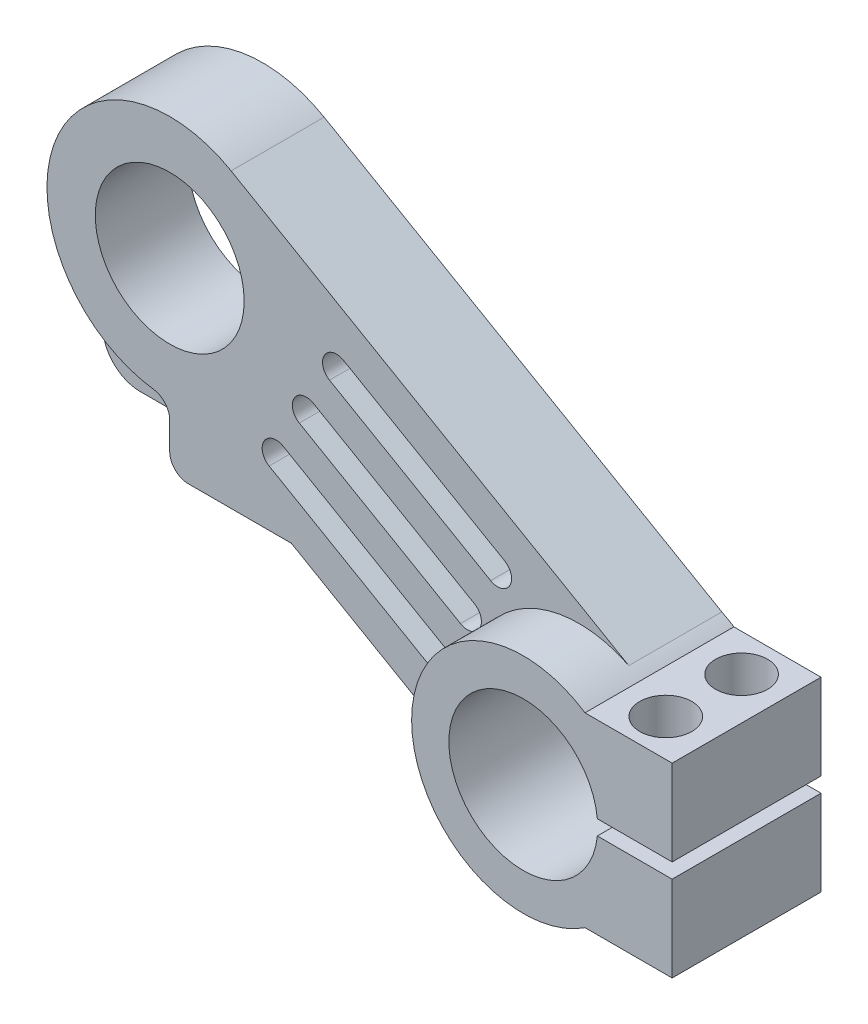
SolidWorks part; units mm, degrees
ref_plane "Alzado" through (0, 0, 0) normal (0, 0, 1) x (1, 0, 0)
ref_plane "Planta" through (0, 0, 0) normal (0, 1, 0) x (1, 0, 0)
ref_plane "Vista lateral" through (0, 0, 0) normal (1, 0, 0) x (0, 0, -1)
sketch "Croquis1" plane through (0, 0, 0) normal (0, 0, 1) x (1, 0, 0)
  line L0 (-285.961, 120) -> (-285.961, 40)
  line L1 (-210, 20) -> (-154.641, 20)
  line L2 (-30, -51.9615) -> (-154.641, 20)
  line L3 (-220, 44.7001) -> (-220, 30)
  line L4 (-187.0195, 177.1239) -> (26.7132, 53.7253)
  line L5 (-265.961, 20) -> (-210, 20)
  line L6 (80, -4) -> (80, -50)
  line L7 (33.1662, 50) -> (80, 50)
  line L9 (33.1662, -50) -> (80, -50)
  line L10 (80, 50) -> (80, 4)
  line L11 (39.7995, 4) -> (80, 4)
  line L13 (39.7995, -4) -> (80, -4)
  line L15 (-60, 34.5741) -> (-146.6025, 84.5741) construction
  line L16 (-63.75, 28.0789) -> (-150.3525, 78.0789)
  line L17 (-56.25, 41.0693) -> (-142.8525, 91.0693)
  line L18 (-76.221, 6.4785) -> (-162.8236, 56.4785) construction
  line L19 (-79.971, -0.0167) -> (-166.5736, 49.9833)
  line L20 (-72.471, 12.9736) -> (-159.0736, 62.9736)
  line L21 (-43.779, 62.6697) -> (-130.3815, 112.6697) construction
  line L22 (-47.529, 56.1745) -> (-134.1315, 106.1745)
  line L23 (-40.029, 69.1649) -> (-126.6315, 119.1649)
  line L24 (-89.971, -17.3372) -> (-30.029, 86.4854) construction
  arc A0 (39.7995, 4) -> (39.7995, -4) centre (0, 0) ccw
  circle A1 centre (-220, 120) radius 40
  arc A2 (33.1662, 50) -> (33.1662, -50) centre (0, 0) ccw
  arc A3 (-187.0195, 177.1239) -> (-228.6835, 54.6131) centre (-220, 120) ccw
  arc A4 (-285.961, 40) -> (-265.961, 20) centre (-265.961, 40) ccw
  arc A5 (-220, 44.7001) -> (-228.6835, 54.6131) centre (-230, 44.7001) ccw
  arc A6 (-210, 20) -> (-220, 30) centre (-210, 30) cw
  arc A7 (-63.75, 28.0789) -> (-56.25, 41.0693) centre (-60, 34.5741) ccw
  arc A8 (-142.8525, 91.0693) -> (-150.3525, 78.0789) centre (-146.6025, 84.5741) ccw
  arc A9 (-79.971, -0.0167) -> (-72.471, 12.9736) centre (-76.221, 6.4785) ccw
  arc A10 (-159.0736, 62.9736) -> (-166.5736, 49.9833) centre (-162.8236, 56.4785) ccw
  arc A11 (-47.529, 56.1745) -> (-40.029, 69.1649) centre (-43.779, 62.6697) ccw
  arc A12 (-126.6315, 119.1649) -> (-134.1315, 106.1745) centre (-130.3815, 112.6697) ccw
  point P16 (-285.961, 20)
  point P19 (-220, 54.039)
  point P28 (-103.3013, 59.5741)
  point P37 (-119.5223, 31.4785)
  point P44 (-87.0803, 87.6697)
  point P51 (0, 0)
  point P52 (0, 0)
  point P53 (0, 0)
  point P54 (-60, 34.5741)
  dimension "D1" = 80
  dimension "D2" = 60
  dimension "D3" = 220
  dimension "D5" = 65.961
  dimension "D8" = 20
  dimension "D9" = 10
  dimension "D10" = 10
  dimension "D17" = 15
  dimension "D4" = 120
  dimension "D6" = 150
  dimension "D7" = 100
  dimension "D11" = 100
  dimension "D12" = 80
  dimension "D13" = 46
  dimension "D14" = 46
  dimension "D15" = 60
  dimension "D16" = 100
  dimension "D18" = 20
  dimension "D19" = 20
extrude "Saliente-Extruir2" add sketch "Croquis1" along normal blind 50 contours A6 L1 L2 A2 L4 A3 A5 L3 A12 L23 A11 L22 A10 L20 A9 L19 A8 L17 A7 L16 A1 region at (-153.9666, 82.8591, 0)
extrude "Saliente-Extruir3" add sketch "Croquis1<4>" along normal blind 80 contours L7 A2 L9 L6 L13 A0 L11 L10 region at (29.0757, 50.366, 0)
sketch "Croquis1<4>" plane through (0, 0, 0) normal (0, 0, 1) x (1, 0, 0) same geometry as "Croquis1"
extrude "Saliente-Extruir4" add sketch "Croquis1<5>" along normal blind 20 contours L5 A6 L3 A5 A3 L0 A4 region at (-257.6209, 46.7535, 0)
sketch "Croquis1<5>" plane through (0, 0, 0) normal (0, 0, 1) x (1, 0, 0) same geometry as "Croquis1"
sketch "Croquis4" plane through (0, 50, 0) normal (0, 1, 0) x (1, 0, 0)
  line L0 (80, -80) -> (80, 0) construction
  line L1 (33.1662, -80) -> (80, -80) construction
  point P0 (57.3094, -20)
  point P1 (56.583, -60)
  dimension "D1" = 23.417
  dimension "D2" = 20
  dimension "D3" = 40
hole_wizard "Refrentado para tornillo con cabeza troncocónica de M52" positions "Croquis3D3" profile "Croquis7" counterbore size "M5" standard "Ansi Metric" end condition through all
sketch3d "Croquis3D3"
  point P0 (56.583, 50, 60)
  point P3 (57.3094, 50, 20)
sketch "Croquis7" plane through (56.583, 50, 60) normal (1, 0, 0) x (0, 0, 1)
  line L0 (0, 0) -> (0, 110)
  line L1 (0, 110) -> (8, 110)
  line L3 (8, 110) -> (8, 20)
  line L4 (8, 20) -> (14, 20)
  line L5 (14, 20) -> (14, 0)
  line L7 (14, 0) -> (0, 0)
  line L11 (0, -6.35) -> (0, 107.95) construction
  dimension "Diámetro de taladro hasta el siguiente" = 16
  dimension "Profundidad de taladro hasta el siguiente" = 110
  dimension "Diámetro de refrentado" = 28
  dimension "Profundidad de refrentado" = 20
